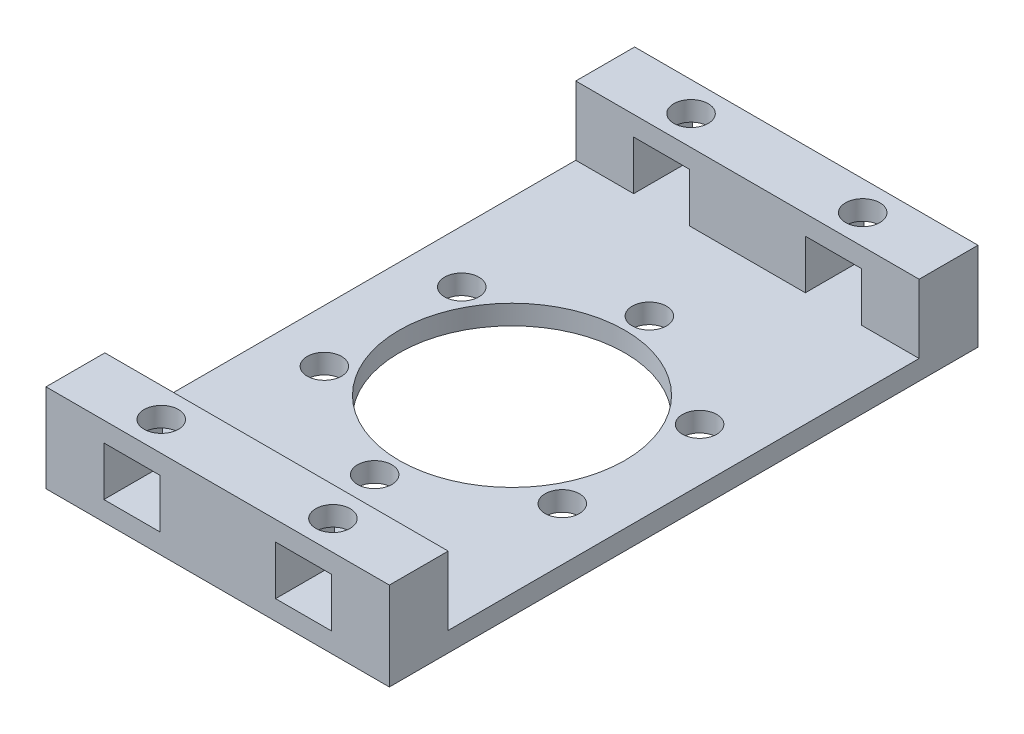
SolidWorks part; units mm, degrees
note: '?' marks a value the reader was unsure of.
ref_plane "前视基准面" through (0, 0, 0) normal (0, 0, 1) x (1, 0, 0)
ref_plane "上视基准面" through (0, 0, 0) normal (0, 1, 0) x (1, 0, 0)
ref_plane "右视基准面" through (0, 0, 0) normal (1, 0, 0) x (0, 0, -1)
sketch "草图1" plane through (0, 0, 0) normal (0, 1, 0) x (1, 0, 0)
  line L1 (-17.5, 30) -> (17.5, 30)
  line L2 (-17.5, 30) -> (-17.5, -30)
  line L3 (-17.5, -30) -> (17.5, -30)
  line L4 (17.5, 30) -> (17.5, -30)
  line L5 (-17.5, 30) -> (17.5, -30) construction
  line L6 (-17.5, -30) -> (17.5, 30) construction
  point P0 (0, 0)
  dimension "D1" = 35
  dimension "D2" = 60
extrude "凸台-拉伸1" add sketch "草图1" along normal blind 2
sketch "草图2" plane through (0, 2, 0) normal (0, 1, 0) x (1, 0, 0)
  circle A0 centre (0, 0) radius 14
  dimension "D1" = 28
sketch "草图3" plane through (0, 2, 0) normal (0, 1, 0) x (1, 0, 0)
  circle A0 centre (0, 0) radius 14 construction
  point P0 (0, 14)
hole_wizard "孔1" positions "草图3" profile "草图4" legacy end condition up to next
sketch "草图4" plane through (0, 2, -14) normal (1, 0, 0) x (0, 0, 1)
  line L0 (0, 0) -> (0, 2)
  line L1 (0, 2) -> (1.75, 2)
  line L2 (1.75, 2) -> (1.75, 0)
  line L3 (1.75, 0) -> (0, 0)
  line L4 (0, 110) -> (0, -10) construction
  dimension "直径" = 3.5
  dimension "深度" = 2
ref_axis "基准轴1" through (0, 0, 0) along (0, 1, 0)?
pattern_circular "阵列(圆周)1" count 6 every 60 about axis through (0, 0, 0) along (0, 1, 0) of "孔1"
sketch "草图5" plane through (0, 2, 0) normal (0, 1, 0) x (1, 0, 0)
  circle A0 centre (0, 0) radius 11.5
  dimension "D1" = 23
extrude "切除-拉伸1" cut sketch "草图5" against normal blind 2
sketch "草图11" plane through (0, 2, 0) normal (0, 1, 0) x (1, 0, 0)
  line L0 (17.5, -30) -> (17.5, 30) construction
  line L1 (-17.5, -30) -> (17.5, -30)
  line L2 (-17.5, -30) -> (-17.5, -24)
  line L3 (-17.5, -24) -> (17.5, -24)
  line L4 (17.5, -30) -> (17.5, -24)
  line L6 (-17.5, 30) -> (17.5, 30)
  line L7 (-17.5, 30) -> (-17.5, 24)
  line L8 (-17.5, 24) -> (17.5, 24)
  line L9 (17.5, 30) -> (17.5, 24)
  dimension "D1" = 6
  dimension "D2" = 6
extrude "凸台-拉伸2" add sketch "草图11" along normal blind 7
sketch "草图12" plane through (0, 0, 30) normal (0, 0, 1) x (1, 0, 0)
  line L0 (-17.5, 9) -> (17.5, 9)
  line L1 (0, 9) -> (-17.5, 9)
  line L2 (-8.75, 9) -> (-8.75, 0)
  line L3 (-17.5, 0) -> (17.5, 0) construction
  line L4 (0, 9) -> (17.5, 9)
  line L5 (8.75, 9) -> (8.75, 0)
  line L7 (-11.6, 2) -> (-5.9, 2)
  line L8 (-11.6, 2) -> (-11.6, 7)
  line L9 (-11.6, 7) -> (-5.9, 7)
  line L10 (-5.9, 2) -> (-5.9, 7)
  line L11 (-11.6, 2) -> (-5.9, 7) construction
  line L12 (-11.6, 7) -> (-5.9, 2) construction
  line L13 (5.9, 2) -> (11.6, 2)
  line L14 (5.9, 2) -> (5.9, 7)
  line L15 (5.9, 7) -> (11.6, 7)
  line L16 (11.6, 2) -> (11.6, 7)
  line L17 (5.9, 2) -> (11.6, 7) construction
  line L18 (5.9, 7) -> (11.6, 2) construction
  line L19 (-11.6, 2) -> (-5.9, 2)
  line L20 (-11.6, 2) -> (-11.6, 7)
  line L21 (-11.6, 7) -> (-5.9, 7)
  line L22 (-5.9, 2) -> (-5.9, 7)
  line L23 (-11.6, 2) -> (-5.9, 7) construction
  line L24 (-11.6, 7) -> (-5.9, 2) construction
  line L25 (11.6, 2) -> (5.9, 2)
  line L26 (11.6, 2) -> (11.6, 7)
  line L27 (11.6, 7) -> (5.9, 7)
  line L28 (5.9, 2) -> (5.9, 7)
  line L29 (11.6, 2) -> (5.9, 7) construction
  line L30 (11.6, 7) -> (5.9, 2) construction
  point P11 (-8.75, 4.5)
  point P16 (8.75, 4.5)
  point P21 (-8.75, 4.5)
  point P22 (8.75, 4.5)
  dimension "D1" = 2
  dimension "D2" = 5
  dimension "D3" = 5.7
  dimension "D4" = 2
  dimension "D5" = 5
  dimension "D6" = 5.7
extrude "切除-拉伸3" cut sketch "草图12" against normal through all contours L9 L8 L7 L2 | L7 L10 L9 L2 | L13 L16 L15 L5 | L15 L14 L13 L5
sketch "草图15" plane through (0, 9, 0) normal (0, 1, 0) x (1, 0, 0)
  line L0 (-17.5, -27) -> (17.5, -27)
  line L1 (-17.5, -24) -> (-17.5, -30) construction
  line L2 (17.5, -30) -> (17.5, -24) construction
  line L3 (0, -27) -> (17.5, -27)
  line L4 (0, -27) -> (-17.5, -27)
  line L5 (-17.5, 27) -> (17.5, 27)
  line L6 (-17.5, 30) -> (-17.5, 24) construction
  line L7 (17.5, 24) -> (17.5, 30) construction
  point P7 (8.75, -27)
  point P8 (-8.75, -27)
  point P15 (8.75, 27)
  point P16 (-8.75, 27)
  dimension "D1" = 8.75
  dimension "D2" = 8.75
sketch "草图18" plane through (0, 9, 0) normal (0, 1, 0) x (1, 0, 0)
sketch "草图20" plane through (0, 9, 0) normal (0, 1, 0) x (1, 0, 0)
  point P0 (-8.75, 27)
  point P3 (8.75, 27)
  point P6 (-8.75, -27)
  point P9 (8.75, -27)
hole_wizard "孔2" positions "草图20" profile "草图19" legacy end condition up to next
sketch "草图19" plane through (-8.75, 9, -27) normal (1, 0, 0) x (0, 0, 1)
  line L0 (0, 0) -> (0, 2)
  line L1 (0, 2) -> (1.75, 2)
  line L2 (1.75, 2) -> (1.75, 0)
  line L3 (1.75, 0) -> (0, 0)
  line L4 (0, 110) -> (0, -10) construction
  dimension "直径" = 3.5
  dimension "深度" = 2
